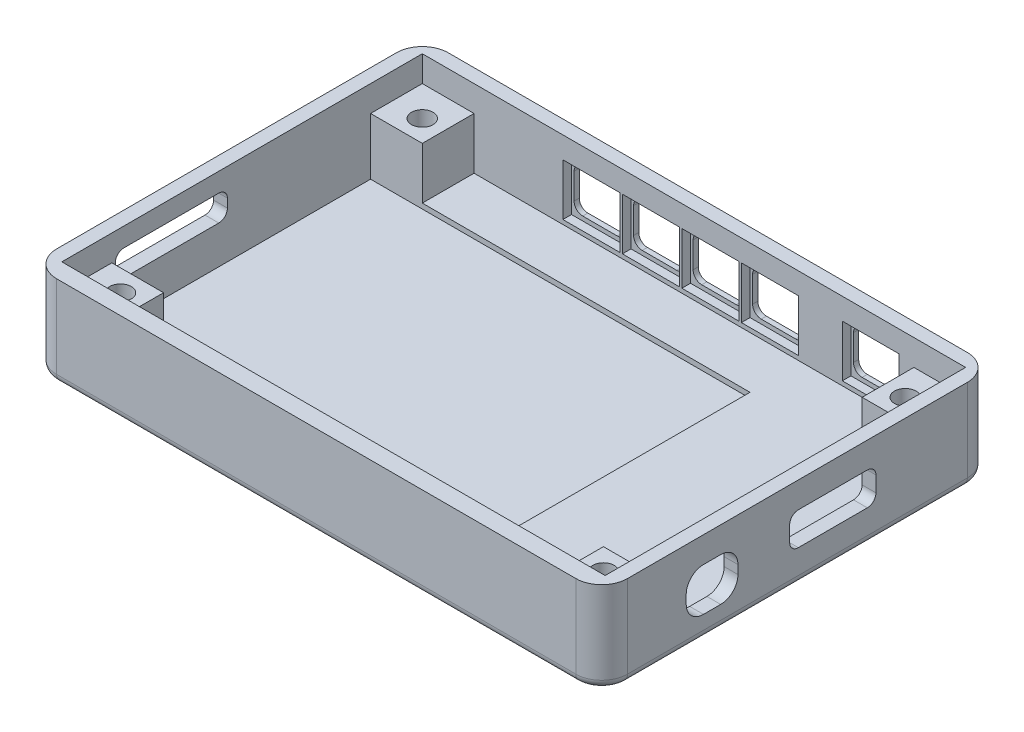
SolidWorks part; units mm, degrees
ref_plane "前视基准面" through (0, 0, 0) normal (0, 0, 1) x (1, 0, 0)
ref_plane "上视基准面" through (0, 0, 0) normal (0, 1, 0) x (1, 0, 0)
ref_plane "右视基准面" through (0, 0, 0) normal (1, 0, 0) x (0, 0, -1)
sketch "草图1" plane through (0, 0, 0) normal (0, 1, 0) x (1, 0, 0)
  line L1 (-31.5, -21) -> (31.5, -21)
  line L2 (-31.5, -21) -> (-31.5, 21)
  line L3 (-31.5, 21) -> (31.5, 21)
  line L4 (31.5, -21) -> (31.5, 21)
  line L5 (-31.5, -21) -> (31.5, 21) construction
  line L6 (-31.5, 21) -> (31.5, -21) construction
  point P0 (0, 0)
  dimension "D1" = 63
  dimension "D2" = 42
extrude "底" add sketch "草图1" against normal blind 1.6
sketch "草图2" plane through (0, 0, 0) normal (0, 1, 0) x (1, 0, 0)
  line L0 (-31.5, 21) -> (-31.5, -21) construction
  line L1 (-31.5, -15) -> (12.5, -15)
  line L2 (-31.5, -15) -> (-31.5, 15)
  line L3 (-31.5, 15) -> (12.5, 15)
  line L4 (12.5, -15) -> (12.5, 15)
  line L5 (-31.5, -15) -> (12.5, 15) construction
  line L6 (-31.5, 15) -> (12.5, -15) construction
  line L7 (31.5, 21) -> (-31.5, 21) construction
  line L8 (-31.5, -21) -> (31.5, -21) construction
  point P0 (-19.9597, 0.5003)
  dimension "D1" = 44
  dimension "D2" = 6
  dimension "D3" = 0
  dimension "D4" = 6
extrude "电池槽" cut sketch "草图2" against normal blind 0.6
sketch "草图4" plane through (0, -1.6, 0) normal (0, -1, 0) x (-1, 0, 0)
  line L0 (-31.5, 21) -> (-31.5, -21)
  line L1 (-31.5, 21) -> (-33.1, 21)
  line L2 (-31.5, -21) -> (-33.1, -21)
  line L3 (-33.1, 21) -> (-33.1, -21)
  line L4 (31.5, 21) -> (31.5, -21)
  line L5 (31.5, 21) -> (33.1, 21)
  line L6 (31.5, -21) -> (33.1, -21)
  line L7 (33.1, 21) -> (33.1, -21)
  dimension "D1" = 1.6
  dimension "D2" = 1.6
extrude "侧边" add sketch "草图4" against normal blind 10.6
sketch "草图5" plane through (0, 0, 0) normal (0, 1, 0) x (1, 0, 0)
  line L0 (-31.5, 21) -> (-31.5, 15)
  line L1 (-31.5, 21) -> (-25.5, 21)
  line L2 (-31.5, 15) -> (-25.5, 15)
  line L3 (-25.5, 21) -> (-25.5, 15)
  line L4 (-31.5, 21) -> (-31.5, 15) construction
  line L5 (25.5, 21) -> (25.5, 15)
  line L6 (25.5, 21) -> (31.5, 21)
  line L7 (25.5, 15) -> (31.5, 15)
  line L8 (31.5, 21) -> (31.5, 15)
  line L9 (-31.5, -15) -> (-31.5, -21)
  line L10 (-31.5, -15) -> (-25.5, -15)
  line L11 (-31.5, -21) -> (-25.5, -21)
  line L12 (-25.5, -15) -> (-25.5, -21)
  line L13 (25.5, -15) -> (25.5, -21)
  line L14 (25.5, -15) -> (31.5, -15)
  line L15 (25.5, -21) -> (31.5, -21)
  line L16 (31.5, -15) -> (31.5, -21)
  dimension "D1" = 6
  dimension "D2" = 6
  dimension "D3" = 6
  dimension "D4" = 6
extrude "螺丝固定" add sketch "草图5" along normal offset from surface (6 mm away) 3 up to face at (-32.3, 9, 0)
sketch "草图6" plane through (0, 9, 0) normal (0, 1, 0) x (1, 0, 0)
  line L0 (-25.5, 15) -> (-25.5, 21) construction
  line L1 (-31.5, 15) -> (-25.5, 15) construction
  circle A0 centre (-28, 17.5) radius 1.25
  circle A1 centre (28, 17.5) radius 1.25
  circle A2 centre (28, -17.5) radius 1.25
  circle A3 centre (-28, -17.5) radius 1.25
  dimension "D1" = 2.5
  dimension "D2" = 2.5
  dimension "D3" = 2.5
  dimension "D4" = 2
  dimension "D5" = 2
extrude "螺丝孔" cut sketch "草图6" against normal up to surface (9 mm away) up to face at (7.3333, 0, 0)
sketch "草图8" plane through (0, 0, 0) normal (0, 1, 0) x (1, 0, 0)
  line L0 (25.5, 21) -> (25.5, 15) construction
  line L1 (-30.5, 20) -> (-25.5, 20)
  line L2 (-30.5, 20) -> (-30.5, 15)
  line L3 (-30.5, 15) -> (-25.5, 15)
  line L4 (-25.5, 20) -> (-25.5, 15)
  line L5 (-30.5, 20) -> (-25.5, 15) construction
  line L6 (-30.5, 15) -> (-25.5, 20) construction
  line L7 (30.5, 20) -> (25.5, 20)
  line L8 (30.5, 20) -> (30.5, 15)
  line L9 (30.5, 15) -> (25.5, 15)
  line L10 (25.5, 20) -> (25.5, 15)
  line L11 (30.5, 20) -> (25.5, 15) construction
  line L12 (30.5, 15) -> (25.5, 20) construction
  line L14 (-30.5, -20) -> (-25.5, -20)
  line L15 (-30.5, -20) -> (-30.5, -15)
  line L16 (-30.5, -15) -> (-25.5, -15)
  line L17 (-25.5, -20) -> (-25.5, -15)
  line L18 (-30.5, -20) -> (-25.5, -15) construction
  line L19 (-30.5, -15) -> (-25.5, -20) construction
  line L20 (30.5, -20) -> (25.5, -20)
  line L21 (30.5, -20) -> (30.5, -15)
  line L22 (30.5, -15) -> (25.5, -15)
  line L23 (25.5, -20) -> (25.5, -15)
  line L24 (30.5, -20) -> (25.5, -15) construction
  line L25 (30.5, -15) -> (25.5, -20) construction
  circle A0 centre (28, 17.5) radius 1.25 construction
  circle A1 centre (28, -17.5) radius 1.25 construction
  circle A2 centre (-28, -17.5) radius 1.25 construction
  circle A3 centre (-28, 17.5) radius 1.25 construction
  circle A4 centre (28, 17.5) radius 1.25 construction
  circle A5 centre (28, -17.5) radius 1.25 construction
  circle A6 centre (-28, -17.5) radius 1.25 construction
  circle A7 centre (-28, 17.5) radius 1.25 construction
sketch "草图9" plane through (0, 0, -21) normal (0, 0, -1) x (-1, 0, 0)
  line L0 (-33.1, 9) -> (-33.1, -1.6)
  line L1 (-33.1, 9) -> (33.1, 9)
  line L2 (-33.1, -1.6) -> (33.1, -1.6)
  line L3 (33.1, 9) -> (33.1, -1.6)
extrude "凸台-拉伸4" add sketch "草图9" along normal blind 1.6
sketch "草图10" plane through (0, 0, -21) normal (0, 0, 1) x (1, 0, 0)
  line L1 (17.2, 0.5) -> (23.8, 0.5)
  line L2 (17.2, 0.5) -> (17.2, 6.5)
  line L3 (17.2, 6.5) -> (23.8, 6.5)
  line L4 (23.8, 0.5) -> (23.8, 6.5)
  line L5 (17.2, 0.5) -> (23.8, 6.5) construction
  line L6 (17.2, 6.5) -> (23.8, 0.5) construction
  line L7 (25.5, 0) -> (-25.5, 0) construction
  line L8 (25.5, 6) -> (25.5, 0) construction
  line L9 (5.5, 0.5) -> (12.1, 0.5)
  line L10 (5.5, 0.5) -> (5.5, 6.5)
  line L11 (5.5, 6.5) -> (12.1, 6.5)
  line L12 (12.1, 0.5) -> (12.1, 6.5)
  line L13 (5.5, 0.5) -> (12.1, 6.5) construction
  line L14 (5.5, 6.5) -> (12.1, 0.5) construction
  line L15 (-1.4, 0.5) -> (5.2, 0.5)
  line L16 (-1.4, 0.5) -> (-1.4, 6.5)
  line L17 (-1.4, 6.5) -> (5.2, 6.5)
  line L18 (5.2, 0.5) -> (5.2, 6.5)
  line L19 (-1.4, 0.5) -> (5.2, 6.5) construction
  line L20 (-1.4, 6.5) -> (5.2, 0.5) construction
  line L21 (-8.3, 0.5) -> (-1.7, 0.5)
  line L22 (-8.3, 0.5) -> (-8.3, 6.5)
  line L23 (-8.3, 6.5) -> (-1.7, 6.5)
  line L24 (-1.7, 0.5) -> (-1.7, 6.5)
  line L25 (-8.3, 0.5) -> (-1.7, 6.5) construction
  line L26 (-8.3, 6.5) -> (-1.7, 0.5) construction
  line L27 (-15.2, 0.5) -> (-8.6, 0.5)
  line L28 (-15.2, 0.5) -> (-15.2, 6.5)
  line L29 (-15.2, 6.5) -> (-8.6, 6.5)
  line L30 (-8.6, 0.5) -> (-8.6, 6.5)
  line L31 (-15.2, 0.5) -> (-8.6, 6.5) construction
  line L32 (-15.2, 6.5) -> (-8.6, 0.5) construction
  point P0 (20.5, 3.5)
  point P11 (8.8, 3.5)
  point P16 (1.9, 3.5)
  point P21 (-5, 3.5)
  point P26 (-11.9, 3.5)
  dimension "D1" = 6.6
  dimension "D2" = 6
  dimension "D3" = 5
  dimension "D4" = 3.5
  dimension "D5" = 2
  dimension "D6" = 4
extrude "按键底" cut sketch "草图10" against normal blind 1
sketch "草图12" plane through (0, 0, -22) normal (0, 0, 1) x (1, 0, 0)
  line L0 (17.2, 6.5) -> (23.8, 0.5) construction
  line L1 (5.8, 2) -> (5.8, 5)
  line L2 (18.5, 1) -> (22.5, 1)
  line L3 (17.5, 2) -> (17.5, 5)
  line L4 (23.8, 0.5) -> (23.8, 6.5)
  line L5 (23.8, 6.5) -> (17.2, 6.5)
  line L6 (17.2, 6.5) -> (17.2, 0.5)
  line L7 (17.2, 0.5) -> (23.8, 0.5)
  line L8 (23.8, 0.5) -> (23.8, 6.5) construction
  line L9 (23.8, 6.5) -> (17.2, 6.5) construction
  line L10 (17.2, 6.5) -> (17.2, 0.5) construction
  line L11 (17.2, 0.5) -> (23.8, 0.5) construction
  line L12 (18.5, 6) -> (22.5, 6)
  line L13 (23.5, 2) -> (23.5, 5)
  line L14 (17.5, 1) -> (23.5, 6) construction
  line L15 (17.5, 6) -> (23.5, 1) construction
  line L16 (6.8, 1) -> (10.8, 1)
  line L17 (6.8, 6) -> (10.8, 6)
  line L18 (11.8, 2) -> (11.8, 5)
  line L19 (-1.1, 2) -> (-1.1, 5)
  line L20 (-0.1, 1) -> (3.9, 1)
  line L21 (-0.1, 6) -> (3.9, 6)
  line L22 (4.9, 2) -> (4.9, 5)
  line L23 (-8, 2) -> (-8, 5)
  line L24 (-7, 1) -> (-3, 1)
  line L25 (-7, 6) -> (-3, 6)
  line L26 (-2, 2) -> (-2, 5)
  line L27 (-14.9, 2) -> (-14.9, 5)
  line L28 (-13.9, 1) -> (-9.9, 1)
  line L29 (-13.9, 6) -> (-9.9, 6)
  line L30 (-8.9, 2) -> (-8.9, 5)
  arc A0 (22.5, 6) -> (23.5, 5) centre (22.5, 5) cw
  arc A1 (22.5, 1) -> (23.5, 2) centre (22.5, 2) ccw
  arc A2 (18.5, 1) -> (17.5, 2) centre (18.5, 2) cw
  arc A3 (17.5, 5) -> (18.5, 6) centre (18.5, 5) cw
  arc A4 (5.8, 5) -> (6.8, 6) centre (6.8, 5) cw
  arc A5 (6.8, 1) -> (5.8, 2) centre (6.8, 2) cw
  arc A6 (10.8, 6) -> (11.8, 5) centre (10.8, 5) cw
  arc A7 (10.8, 1) -> (11.8, 2) centre (10.8, 2) ccw
  arc A8 (-1.1, 5) -> (-0.1, 6) centre (-0.1, 5) cw
  arc A9 (-0.1, 1) -> (-1.1, 2) centre (-0.1, 2) cw
  arc A10 (3.9, 6) -> (4.9, 5) centre (3.9, 5) cw
  arc A11 (3.9, 1) -> (4.9, 2) centre (3.9, 2) ccw
  arc A12 (-8, 5) -> (-7, 6) centre (-7, 5) cw
  arc A13 (-7, 1) -> (-8, 2) centre (-7, 2) cw
  arc A14 (-3, 6) -> (-2, 5) centre (-3, 5) cw
  arc A15 (-3, 1) -> (-2, 2) centre (-3, 2) ccw
  arc A16 (-14.9, 5) -> (-13.9, 6) centre (-13.9, 5) cw
  arc A17 (-13.9, 1) -> (-14.9, 2) centre (-13.9, 2) cw
  arc A18 (-9.9, 6) -> (-8.9, 5) centre (-9.9, 5) cw
  arc A19 (-9.9, 1) -> (-8.9, 2) centre (-9.9, 2) ccw
  point P2 (20.5, 3.5)
  dimension "D4" = 1
  dimension "D2" = 6
  dimension "D3" = 5
  dimension "D1" = 0
  dimension "D5" = 2
  dimension "D6" = 4
extrude "按键头" cut sketch "草图12" against normal up to next
fillet "圆角4" radius 1 3 edges at (-33.1, -1.6, -0.8) (33.1, -1.6, -0.8) (0, -1.6, -22.6)
fillet "圆角5" radius 3 4 edges at (-32.8071, -1.3071, -22.3071) (32.8071, -1.3071, -22.3071) (33.1, 4.2, -22.6) (-33.1, 4.2, -22.6)
sketch "草图15" plane through (0, 9, 0) normal (0, 1, 0) x (1, 0, 0)
  line L8 (-31.5, 21) -> (31.5, 21)
  line L10 (-31.5, 21) -> (31.5, 21)
  line L16 (33.1, -21) -> (33.1, 19.6)
  line L17 (30.1, 22.6) -> (-30.1, 22.6)
  line L18 (-33.1, 19.6) -> (-33.1, -21)
  line L19 (-33.1, -21) -> (-31.5, -21)
  line L22 (-31.5, -21) -> (-31.5, 21)
  line L28 (31.5, 21) -> (31.5, -21)
  line L31 (31.5, -21) -> (33.1, -21)
  line L32 (33.1, -21) -> (33.1, 19.6)
  line L33 (30.1, 22.6) -> (-30.1, 22.6)
  line L34 (-33.1, 19.6) -> (-33.1, -21)
  line L35 (-33.1, -21) -> (-31.5, -21)
  line L38 (-31.5, -21) -> (-31.5, 21)
  line L44 (31.5, 21) -> (31.5, -21)
  line L47 (31.5, -21) -> (33.1, -21)
  arc A2 (33.1, 19.6) -> (30.1, 22.6) centre (30.1, 19.6) ccw
  arc A3 (-30.1, 22.6) -> (-33.1, 19.6) centre (-30.1, 19.6) ccw
  arc A4 (33.1, 19.6) -> (30.1, 22.6) centre (30.1, 19.6) ccw
  arc A5 (-30.1, 22.6) -> (-33.1, 19.6) centre (-30.1, 19.6) ccw
  dimension "D1" = 0
sketch "草图16" plane through (-31.5, 0, 0) normal (1, 0, 0) x (0, 0, -1)
  line L1 (-14.6, 5.8) -> (-14.6, 4.8)
  line L2 (-1.6, 5.8) -> (-1.6, 4.8)
  line L3 (-13.6, 3.8) -> (-2.6, 3.8)
  line L4 (-21, 9) -> (21, 9) construction
  line L5 (-15, 6) -> (-15, -0.6) construction
  line L6 (-13.6, 6.8) -> (-2.6, 6.8)
  arc A0 (-14.6, 4.8) -> (-13.6, 3.8) centre (-13.6, 4.8) ccw
  arc A1 (-1.6, 4.8) -> (-2.6, 3.8) centre (-2.6, 4.8) cw
  arc A2 (-13.6, 6.8) -> (-14.6, 5.8) centre (-13.6, 5.8) ccw
  arc A3 (-2.6, 6.8) -> (-1.6, 5.8) centre (-2.6, 5.8) cw
  point P10 (-14.6, 3.8)
  point P13 (-1.6, 3.8)
  dimension "D4" = 1
  dimension "D2" = 1
  dimension "D1" = 13
  dimension "D3" = 0.4
  dimension "D5" = 2.2
extrude "tf口" cut sketch "草图16" against normal up to next
sketch "草图17" plane through (31.5, 0, 0) normal (-1, 0, 0) x (0, 0, 1)
  line L1 (7, 4) -> (7, 3)
  line L2 (13, 4) -> (13, 3)
  line L3 (9, 1) -> (11, 1)
  line L4 (-21, 9) -> (21, 9) construction
  line L5 (15, -0.6) -> (15, 6) construction
  line L7 (1, 5) -> (1, 3.2)
  line L8 (-9, 5) -> (-9, 3.2)
  line L9 (0, 2.2) -> (-8, 2.2)
  line L10 (-8, 6) -> (0, 6)
  line L12 (9, 6) -> (11, 6)
  arc A0 (13, 3) -> (11, 1) centre (11, 3) cw
  arc A1 (7, 3) -> (9, 1) centre (9, 3) ccw
  arc A2 (1, 3.2) -> (0, 2.2) centre (0, 3.2) cw
  arc A3 (-9, 3.2) -> (-8, 2.2) centre (-8, 3.2) ccw
  arc A4 (0, 6) -> (1, 5) centre (0, 5) cw
  arc A5 (-8, 6) -> (-9, 5) centre (-8, 5) ccw
  arc A6 (11, 6) -> (13, 4) centre (11, 4) cw
  arc A7 (9, 6) -> (7, 4) centre (9, 4) ccw
  point P10 (13, 1)
  point P13 (7, 1)
  point P14 (1, 6)
  point P22 (1, 2.2)
  point P25 (-9, 2.2)
  dimension "D4" = 2
  dimension "D8" = 1
  dimension "D2" = 1
  dimension "D7" = 2
  dimension "D1" = 6
  dimension "D3" = 2
  dimension "D5" = 10
  dimension "D6" = 14
  dimension "D9" = 3
  dimension "D10" = 1.8
  dimension "D11" = 1
extrude "耳机和usb口" cut sketch "草图17" against normal up to next
sketch "草图18" plane through (0, 0, 21) normal (0, 0, 1) x (1, 0, 0)
  line L0 (33.1, 9) -> (33.1, -0.6) construction
  line L1 (-32.1, -1.6) -> (32.1, -1.6) construction
  line L2 (-33.1, 9) -> (-33.1, -0.6) construction
  line L3 (33.1, 9) -> (33.1, -0.6)
  line L4 (-32.1, -1.6) -> (32.1, -1.6)
  line L5 (-33.1, 9) -> (-33.1, -0.6)
  line L6 (-33.1, 9) -> (33.1, 9)
  arc A0 (32.1, -1.6) -> (33.1, -0.6) centre (32.1, -0.6) ccw construction
  arc A1 (-33.1, -0.6) -> (-32.1, -1.6) centre (-32.1, -0.6) ccw construction
  arc A2 (32.1, -1.6) -> (33.1, -0.6) centre (32.1, -0.6) ccw
  arc A3 (-33.1, -0.6) -> (-32.1, -1.6) centre (-32.1, -0.6) ccw
extrude "封底" add sketch "草图18" along normal blind 1.8
fillet "圆角7" radius 3 2 edges at (33.1, 4.2, 22.8) (-33.1, 4.2, 22.8) tangent propagation no
fillet "圆角8" radius 1 3 edges at (-31.1705, -1.6, 22.6025) (31.1705, -1.6, 22.6025) (0, -1.6, 22.8)
sketch "草图19" plane through (0, 0, 21) normal (0, 0, -1) x (-1, 0, 0)
  line L8 (31.5, 9) -> (-31.5, 9)
  line L9 (-31.5, 9) -> (-31.5, 6)
  line L10 (-31.5, 6) -> (-25.5, 6)
  line L11 (-25.5, 6) -> (-25.5, 0)
  line L12 (-25.5, 0) -> (25.5, 0)
  line L13 (25.5, 0) -> (25.5, 6)
  line L14 (25.5, 6) -> (31.5, 6)
  line L15 (31.5, 6) -> (31.5, 9)
  line L16 (31.5, 9) -> (-31.5, 9)
  line L17 (-31.5, 9) -> (-31.5, 6)
  line L18 (-31.5, 6) -> (-25.5, 6)
  line L19 (-25.5, 6) -> (-25.5, 0)
  line L20 (-25.5, 0) -> (25.5, 0)
  line L21 (25.5, 0) -> (25.5, 6)
  line L22 (25.5, 6) -> (31.5, 6)
  line L23 (31.5, 6) -> (31.5, 9)
  dimension "D1" = 0
extrude "凸台-拉伸5" add sketch "草图19" along normal blind 0.2
sketch "草图25" plane through (0, 0, 0) normal (0, 1, 0) x (1, 0, 0)
  circle A0 centre (25.5, 12) radius 1
  point P0 (28, 17.5)
  dimension "D1" = 2
  dimension "D2" = 2.5
  dimension "D3" = 5.5
extrude "BOOT孔" cut sketch "草图25" against normal up to next
sketch "草图27" plane through (0, 0, -21) normal (0, 0, 1) x (1, 0, 0)
  line L4 (5.5, 0.5) -> (12.1, 0.5)
  line L5 (12.1, 0.5) -> (12.1, 6.5)
  line L6 (12.1, 6.5) -> (5.5, 6.5)
  line L7 (5.5, 6.5) -> (5.5, 0.5)
  line L8 (31.5, 6) -> (31.5, 9)
  line L9 (31.5, 9) -> (-31.5, 9)
  line L10 (-31.5, 9) -> (-31.5, 6)
  line L11 (-31.5, 6) -> (-25.5, 6)
  line L12 (-25.5, 6) -> (-25.5, 0)
  line L13 (-25.5, 0) -> (25.5, 0)
  line L14 (25.5, 0) -> (25.5, 6)
  line L15 (25.5, 6) -> (31.5, 6)
  line L16 (31.5, 6) -> (31.5, 9)
  line L17 (31.5, 9) -> (-31.5, 9)
  line L18 (-31.5, 9) -> (-31.5, 6)
  line L19 (-31.5, 6) -> (-25.5, 6)
  line L20 (-25.5, 6) -> (-25.5, 0)
  line L21 (-25.5, 0) -> (25.5, 0)
  line L22 (25.5, 0) -> (25.5, 6)
  line L23 (25.5, 6) -> (31.5, 6)
  line L24 (5.5, 0.5) -> (12.1, 0.5)
  line L25 (12.1, 0.5) -> (12.1, 6.5)
  line L26 (12.1, 6.5) -> (5.5, 6.5)
  line L27 (5.5, 6.5) -> (5.5, 0.5)
  line L28 (17.2, 0.5) -> (23.8, 0.5)
  line L29 (23.8, 0.5) -> (23.8, 6.5)
  line L30 (23.8, 6.5) -> (17.2, 6.5)
  line L31 (17.2, 6.5) -> (17.2, 0.5)
  line L32 (17.2, 0.5) -> (23.8, 0.5)
  line L33 (23.8, 0.5) -> (23.8, 6.5)
  line L34 (23.8, 6.5) -> (17.2, 6.5)
  line L35 (17.2, 6.5) -> (17.2, 0.5)
  line L36 (-15.2, 0.5) -> (-8.6, 0.5)
  line L37 (-8.6, 0.5) -> (-8.6, 6.5)
  line L38 (-8.6, 6.5) -> (-15.2, 6.5)
  line L39 (-15.2, 6.5) -> (-15.2, 0.5)
  line L40 (-15.2, 0.5) -> (-8.6, 0.5)
  line L41 (-8.6, 0.5) -> (-8.6, 6.5)
  line L42 (-8.6, 6.5) -> (-15.2, 6.5)
  line L43 (-15.2, 6.5) -> (-15.2, 0.5)
  line L44 (-8.3, 0.5) -> (-1.7, 0.5)
  line L45 (-1.7, 0.5) -> (-1.7, 6.5)
  line L46 (-1.7, 6.5) -> (-8.3, 6.5)
  line L47 (-8.3, 6.5) -> (-8.3, 0.5)
  line L48 (-8.3, 0.5) -> (-1.7, 0.5)
  line L49 (-1.7, 0.5) -> (-1.7, 6.5)
  line L50 (-1.7, 6.5) -> (-8.3, 6.5)
  line L51 (-8.3, 6.5) -> (-8.3, 0.5)
  line L52 (-1.4, 0.5) -> (5.2, 0.5)
  line L53 (5.2, 0.5) -> (5.2, 6.5)
  line L54 (5.2, 6.5) -> (-1.4, 6.5)
  line L55 (-1.4, 6.5) -> (-1.4, 0.5)
  line L56 (-1.4, 0.5) -> (5.2, 0.5)
  line L57 (5.2, 0.5) -> (5.2, 6.5)
  line L58 (5.2, 6.5) -> (-1.4, 6.5)
  line L59 (-1.4, 6.5) -> (-1.4, 0.5)
  dimension "D1" = 0
  dimension "D2" = 0
  dimension "D3" = 0
  dimension "D4" = 0
  dimension "D5" = 0
  dimension "D6" = 0
